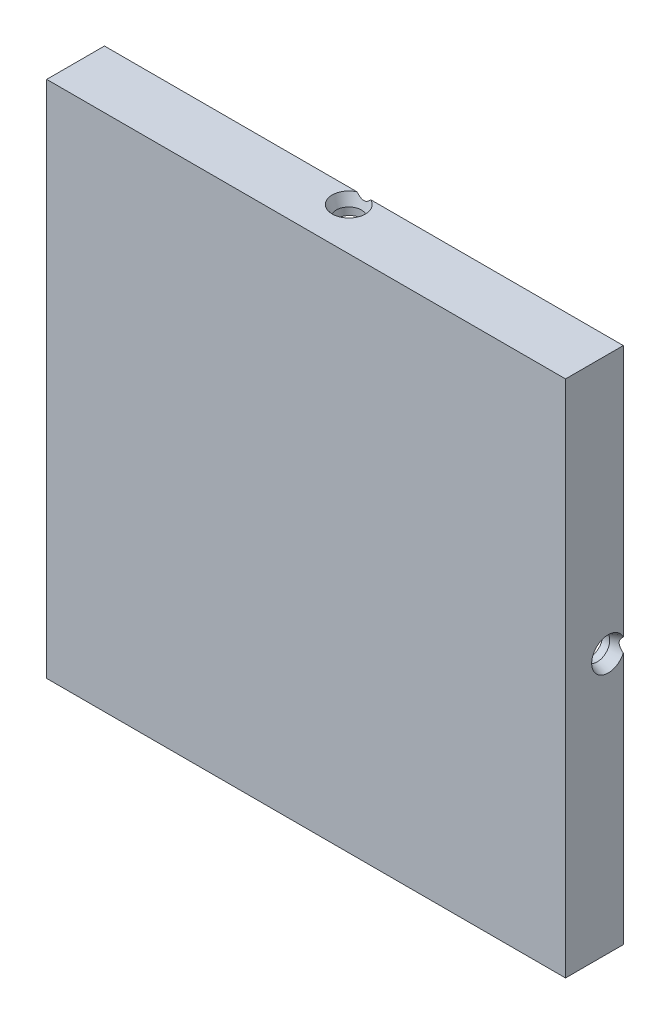
SolidWorks part; units mm, degrees
note: The reader was unsure of these and kept them because the rebuilt part matched: shared geometry of "Sketch1<3>", "Sketch1<4>".
material "Custom Plastic"
ref_plane "Front Plane" through (0, 0, 0) normal (0, 0, 1) x (1, 0, 0)
ref_plane "Top Plane" through (0, 0, 0) normal (0, 1, 0) x (1, 0, 0)
ref_plane "Right Plane" through (0, 0, 0) normal (1, 0, 0) x (0, 0, -1)
sketch "Sketch1" plane through (0, 0, 0) normal (0, 0, 1) x (1, 0, 0)
  line L0 (0, 0) -> (-9.924, -56.2818) construction
  line L1 (-81.9785, 81.9785) -> (81.9785, 81.9785)
  line L2 (-81.9785, 81.9785) -> (-81.9785, -81.9785)
  line L3 (-81.9785, -81.9785) -> (81.9785, -81.9785)
  line L4 (81.9785, 81.9785) -> (81.9785, -81.9785)
  line L5 (0, 0) -> (0, -76.2) construction
  line L6 (-27.4443, 76.2) -> (31.5245, 76.2) construction
  line L7 (0, 0) -> (-26.8517, -9.7732) construction
  circle A0 centre (0, 0) radius 76.2
  circle A1 centre (-9.924, -56.2818) radius 3.0163
  circle A2 centre (0, 0) radius 3.0162
  circle A3 centre (-43.7794, 36.7353) radius 3.0163
  circle A4 centre (53.7034, 19.5465) radius 3.0163
  circle A5 centre (-69.2785, 69.2785) radius 3.3337
  circle A6 centre (69.2785, 69.2785) radius 3.3337
  circle A7 centre (69.2785, -69.2785) radius 3.3337
  circle A8 centre (-69.2785, -69.2785) radius 3.3337
  circle A9 centre (-26.8517, -9.7732) radius 3.048
  point P12 (0, 81.9785)
  point P18 (0, 0)
  point P23 (-81.9785, 0)
  point P29 (0, 0)
  dimension "D1" = 152.4
  dimension "D4" = 6.0325
  dimension "D5" = 6.0325
  dimension "D7" = 6.6675
  dimension "D14" = 6.096
  dimension "D2" = 57.15
  dimension "D3" = 10
  dimension "D8" = 12.7
  dimension "D9" = 90
  dimension "D10" = 12.7
  dimension "D11" = 4
  dimension "D12" = 81.9785
  dimension "D13" = 5.7785
  dimension "D15" = 28.575
  dimension "D16" = 60
  dimension "D6" = 3
extrude "Boss-Extrude1" add sketch "Sketch1" along normal blind 8.7312 contours L4 L1 L2 L3 A8 A7 A6 A5 A0 | A6 | A5 | A8 | A7 | A1 | A3 | A4 | A0 A4 A3 A2 A1 | A2
extrude "Boss-Extrude2" add sketch "Sketch1<3>" against normal blind 9.525 contours L4 L1 L2 L3 A8 A7 A6 A5 A0 | A4 | A1 | A2 | A3 | A9
sketch "Sketch1<3>" plane through (0, 0, 0) normal (0, 0, 1) x (1, 0, 0) same geometry as "Sketch1"
extrude "Boss-Extrude3" add sketch "Sketch1<4>" against normal blind 18.3515 contours A2
sketch "Sketch1<4>" plane through (0, 0, 0) normal (0, 0, 1) x (1, 0, 0) same geometry as "Sketch1"
sketch "Sketch2" plane through (0, 81.9785, 0) normal (0, 1, 0) x (1, 0, 0)
  line L0 (-81.9785, 9.525) -> (81.9785, 9.525) construction
  circle A0 centre (0, 4.7625) radius 3.9688
  dimension "D1" = 7.9375
  dimension "D2" = 4.7625
extrude "Cut-Extrude1" cut sketch "Sketch2" against normal up to next
pattern_circular "CirPattern1" count 4 over 360 about axis through (0, 0, -9.525) along (0, 0, 1) of "Cut-Extrude1"
sketch "Sketch4" plane through (0, 0, 0) normal (0, 0, -1) x (-1, 0, 0)
  line L0 (-46.8941, 0) -> (-25.0102, 0) construction
  line L1 (-46.8941, 1.27) -> (-25.0102, 1.27)
  line L2 (-46.8941, -1.27) -> (-25.0102, -1.27)
  arc A0 (-46.8941, 1.27) -> (-46.8941, -1.27) centre (-46.8941, 0) ccw
  arc A1 (-25.0102, -1.27) -> (-25.0102, 1.27) centre (-25.0102, 0) ccw
  point P2 (-35.9522, 0)
  dimension "D1" = 2.54
extrude "Cut-Extrude2" [suppressed] cut sketch "Sketch4" against normal blind 5.08
fillet "Fillet3" [suppressed] radius 1.905
sketch "Sketch5" plane through (0, 0, 8.7312) normal (0, 0, 1) x (1, 0, 0)
  circle A0 centre (-26.8517, -9.7732) radius 3.048
extrude "Boss-Extrude4" add sketch "Sketch5" against normal blind 9.525
chamfer "Chamfer1" distance 1.27 angle 70 4 edges at (-81.9785, 0, -0.7938) (0, -81.9785, -0.7938) (81.9785, 0, -0.7938) (0, 81.9785, -0.7938)
sketch "Sketch6" plane through (0, 0, 8.7312) normal (0, 0, 1) x (1, 0, 0)
  line L0 (0, 0) -> (8.9923, 50.998) construction
  line L1 (7.48, 40.5928) -> (6.8547, 40.7031)
  line L2 (10.5705, 36.1791) -> (9.1371, 28.0495)
  line L3 (2.4409, 37.6126) -> (1.0075, 29.483)
  line L4 (4.7233, 24.959) -> (4.098, 25.0693)
  line L5 (0, 0) -> (0, 48.6565) construction
  arc A0 (10.5705, 36.1791) -> (7.48, 40.5928) centre (6.8184, 36.8407) ccw
  arc A1 (9.1371, 28.0495) -> (4.7233, 24.959) centre (5.3849, 28.7111) cw
  arc A2 (4.098, 25.0693) -> (1.0075, 29.483) centre (4.7596, 28.8214) cw
  arc A3 (2.4409, 37.6126) -> (6.8547, 40.7031) centre (6.1931, 36.951) cw
  point P3 (7.1673, 40.6479)
  dimension "D1" = 3.81
  dimension "D2" = 41.275
  dimension "D3" = 25.4
  dimension "D4" = 8.255
  dimension "D5" = 10
extrude "Boss-Extrude5" add sketch "Sketch6" against normal up to surface (18.2563 mm away) up to face at (56.7197, 19.5465, -9.525)
fillet "Fillet4" radius 2.54 8 edges at (9.9394, 39.026, -9.525) (7.1673, 40.6479, -9.525) (4.0077, 40.0719, -9.525) (1.7242, 33.5478, -9.525) (1.6386, 26.636, -9.525) (4.4107, 25.0141, -9.525) (7.5703, 25.5901, -9.525) (9.8538, 32.1143, -9.525)
